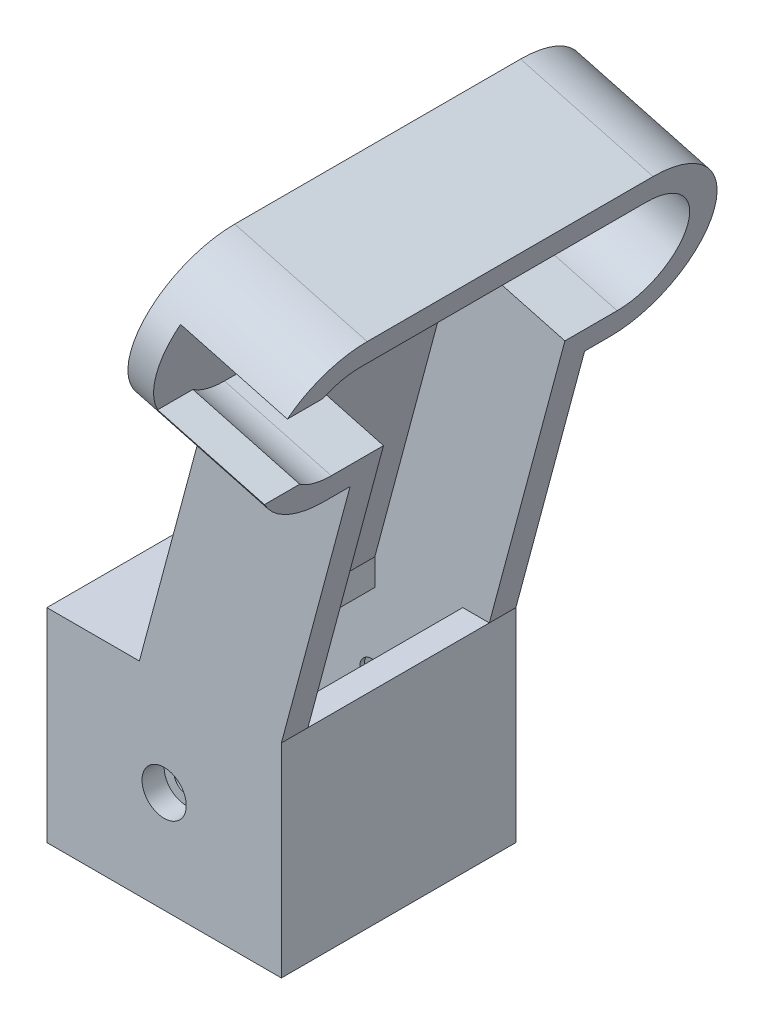
SolidWorks part; units mm, degrees
ref_plane "Front Plane" through (0, 0, 0) normal (0, 0, 1) x (1, 0, 0)
ref_plane "Top Plane" through (0, 0, 0) normal (0, 1, 0) x (1, 0, 0)
ref_plane "Right Plane" through (0, 0, 0) normal (1, 0, 0) x (0, 0, -1)
sketch "Sketch1" plane through (0, 0, 0) normal (0, 1, 0) x (1, 0, 0)
  line L0 (-20.5, 20.5) -> (-20.5, -20.5)
  line L1 (-20, 20) -> (20, 20) construction
  line L2 (-20, 20) -> (-20, -20) construction
  line L3 (-20, -20) -> (20, -20) construction
  line L4 (20, 20) -> (20, -20) construction
  line L5 (-20, 20) -> (20, -20) construction
  line L6 (-20, -20) -> (20, 20) construction
  line L7 (-20.5, -20.5) -> (20.5, -20.5)
  line L8 (20.5, 20.5) -> (20.5, -20.5)
  line L9 (-20.5, 20.5) -> (20.5, 20.5)
  line L10 (-26.5, 26.5) -> (-26.5, -26.5)
  line L11 (-26.5, -26.5) -> (26.5, -26.5)
  line L12 (26.5, 26.5) -> (26.5, -26.5)
  line L13 (-26.5, 26.5) -> (26.5, 26.5)
  point P1 (0, 0)
  dimension "D1" = 40
  dimension "D2" = 0.5
  dimension "D3" = 6
extrude "Boss-Extrude1" add sketch "Sketch1" along normal blind 40
sketch "Sketch2" plane through (0, 40, 0) normal (0, 1, 0) x (1, 0, 0)
  line L4 (26.5, 26.5) -> (-26.5, 26.5)
  line L5 (-26.5, 26.5) -> (-26.5, -26.5)
  line L6 (-26.5, -26.5) -> (26.5, -26.5)
  line L7 (26.5, -26.5) -> (26.5, 26.5)
  line L8 (26.5, 26.5) -> (-26.5, 26.5)
  line L9 (-26.5, 26.5) -> (-26.5, -26.5)
  line L10 (-26.5, -26.5) -> (26.5, -26.5)
  line L11 (26.5, -26.5) -> (26.5, 26.5)
  dimension "D1" = 0
extrude "Boss-Extrude2" add sketch "Sketch2" along normal blind 6
ref_plane "Plane1" through (13.2248, -3.5436, 0) normal (-0.9659, 0.2588, 0) x (0, 0, -1)
sketch "Sketch3" plane through (13.2248, -3.5436, 0) normal (-0.9659, 0.2588, 0) x (0, 0, -1)
  line L1 (26.5, -31.2913) -> (-26.5, -31.2913)
  line L2 (26.5, -31.2913) -> (26.5, -111.2913)
  line L3 (26.5, -111.2913) -> (-26.5, -111.2913)
  line L4 (-26.5, -31.2913) -> (-26.5, -111.2913)
  line L5 (20.5, -37.2913) -> (20.5, -105.2913)
  line L6 (20.5, -105.2913) -> (-20.5, -105.2913)
  line L7 (-20.5, -37.2913) -> (-20.5, -105.2913)
  line L8 (20.5, -37.2913) -> (-20.5, -37.2913)
  line L9 (-26.5, -51.2913) -> (-26.5, -6.8587) construction
  line L10 (26.5, -51.2913) -> (26.5, -6.8587) construction
  line L11 (-26.5, -51.2913) -> (26.5, -51.2913) construction
  point P5 (-26.2486, -51.2913)
  point P6 (0, 0)
  point P13 (0, 0)
  dimension "D1" = 80
  dimension "D3" = 20
  dimension "D2" = 6
extrude "Boss-Extrude3" add sketch "Sketch3" along normal blind 31
sketch "Sketch4" plane through (13.2248, -3.5436, 0) normal (0.9659, -0.2588, 0) x (0, 0, -1)
  line L0 (-32.3, 129.9913) -> (32.3, 129.9913) construction
  line L1 (-32.3, 142.6913) -> (32.3, 142.6913)
  line L2 (-32.3, 117.2913) -> (32.3, 117.2913)
  line L3 (-32.3, 148.6913) -> (32.3, 148.6913)
  line L4 (-32.3, 111.2913) -> (32.3, 111.2913)
  line L5 (0, 111.2913) -> (0, 51.2913) construction
  line L6 (-26.5, 111.2913) -> (26.5, 111.2913) construction
  line L7 (-20.5, 51.2913) -> (20.5, 51.2913) construction
  arc A0 (-32.3, 142.6913) -> (-32.3, 117.2913) centre (-32.3, 129.9913) ccw
  arc A1 (32.3, 117.2913) -> (32.3, 142.6913) centre (32.3, 129.9913) ccw
  arc A2 (32.3, 111.2913) -> (32.3, 148.6913) centre (32.3, 129.9913) ccw
  arc A3 (-32.3, 148.6913) -> (-32.3, 111.2913) centre (-32.3, 129.9913) ccw
  point P2 (0, 129.9913)
  point P19 (0, 0)
  point P20 (0, 111.2913)
  dimension "D1" = 25.4
  dimension "D2" = 64.6
  dimension "D3" = 6
extrude "Boss-Extrude4" add sketch "Sketch4" against normal up to surface (31 mm away) up to face at (2.8577, 77.5406, 0)
sketch "Sketch5" plane through (-16.7189, 4.4798, 0) normal (-0.9659, 0.2588, 0) x (0, 0, 1)
  line L0 (-20.5, 42.9849) -> (20.5, 42.9849)
  line L10 (20.5, 42.9849) -> (26.5, 42.9849)
  line L11 (26.5, 42.9849) -> (26.5, 111.2913)
  line L12 (26.5, 111.2913) -> (32.3, 111.2913)
  line L13 (32.3, 148.6913) -> (-32.3, 148.6913)
  line L14 (-32.3, 111.2913) -> (-26.5, 111.2913)
  line L15 (-26.5, 111.2913) -> (-26.5, 42.9849)
  line L16 (-26.5, 42.9849) -> (-20.5, 42.9849)
  line L17 (-20.5, 42.9849) -> (-20.5, 105.2913)
  line L18 (-20.5, 105.2913) -> (20.5, 105.2913)
  line L19 (20.5, 105.2913) -> (20.5, 42.9849)
  line L20 (20.5, 42.9849) -> (26.5, 42.9849)
  line L21 (26.5, 42.9849) -> (26.5, 111.2913)
  line L22 (26.5, 111.2913) -> (32.3, 111.2913)
  line L23 (32.3, 148.6913) -> (-32.3, 148.6913)
  line L24 (-32.3, 111.2913) -> (-26.5, 111.2913)
  line L25 (-26.5, 111.2913) -> (-26.5, 42.9849)
  line L26 (-26.5, 42.9849) -> (-20.5, 42.9849)
  line L27 (-20.5, 42.9849) -> (-20.5, 105.2913) construction
  line L28 (-20.5, 105.2913) -> (20.5, 105.2913) construction
  line L29 (20.5, 105.2913) -> (20.5, 42.9849) construction
  arc A2 (32.3, 111.2913) -> (32.3, 148.6913) centre (32.3, 129.9913) ccw
  arc A3 (-32.3, 148.6913) -> (-32.3, 111.2913) centre (-32.3, 129.9913) ccw
  arc A4 (32.3, 111.2913) -> (32.3, 148.6913) centre (32.3, 129.9913) ccw
  arc A5 (-32.3, 148.6913) -> (-32.3, 111.2913) centre (-32.3, 129.9913) ccw
  dimension "D1" = 0
extrude "Boss-Extrude5" add sketch "Sketch5" against normal blind 6
sketch "Sketch6" plane through (13.2248, -3.5436, 0) normal (0.9659, -0.2588, 0) x (0, 0, -1)
  line L0 (-32.3, 117.2913) -> (32.3, 117.2913) construction
  line L1 (-20.5, 105.2913) -> (20.5, 105.2913)
  line L2 (-20.5, 105.2913) -> (-20.5, 117.2913)
  line L3 (-20.5, 117.2913) -> (20.5, 117.2913)
  line L4 (20.5, 105.2913) -> (20.5, 117.2913)
  line L5 (20.5, 105.2913) -> (20.5, 44.5926) construction
extrude "Cut-Extrude1" cut sketch "Sketch6" against normal up to surface (25 mm away) up to face at (8.4731, 75.3152, 0)
sketch "Sketch7" plane through (-16.7189, 4.4798, 0) normal (0.9659, -0.2588, 0) x (0, 0, -1)
  line L0 (-22.5, 129.9913) -> (22.5, 129.9913) construction
  line L1 (-20.5, 117.2913) -> (-20.5, 142.6913) construction
  line L2 (32.3, 142.6913) -> (-32.3, 142.6913) construction
  point P0 (-22.5, 129.9913)
  point P1 (22.5, 129.9913)
  point P2 (0, 129.9913)
  point P9 (-20.5, 129.9913)
  dimension "D1" = 45
sketch "Sketch12" plane through (-16.7189, 4.4798, 0) normal (-0.9659, 0.2588, 0) x (0, 0, 1)
  point P0 (22.5, 129.9913)
  point P3 (-22.5, 129.9913)
hole_wizard "CBORE for M3 SHCS2" positions "Sketch12" profile "Sketch11" counterbore size "M3" standard "ANSI Metric" end condition up to next
sketch "Sketch11" plane through (16.9254, 130.0418, 22.5) normal (0, 0, 1) x (-0.2588, -0.9659, 0)
  line L0 (0, 0) -> (0, 6)
  line L1 (0, 6) -> (1.7, 6)
  line L3 (1.7, 6) -> (1.7, 3)
  line L4 (1.7, 3) -> (3.25, 3)
  line L5 (3.25, 3) -> (3.25, 0)
  line L7 (3.25, 0) -> (0, 0)
  line L11 (0, -6.35) -> (0, 107.95) construction
  dimension "Thru Hole Dia." = 3.4
  dimension "Thru Hole Depth" = 6
  dimension "C'Bore Dia." = 6.5
  dimension "C'Bore Depth" = 3
sketch "Sketch13" plane through (0, 0, 0) normal (0, 0, 1) x (1, 0, 0)
  line L0 (49.4572, 131.6776) -> (44.2809, 112.3591)
  line L1 (42.0291, 103.9555) -> (51.709, 140.0812) construction
  line L2 (44.2809, 112.3591) -> (20.1327, 118.8296)
  line L3 (20.1327, 118.8296) -> (25.3091, 138.1481)
  line L4 (25.3091, 138.1481) -> (49.4572, 131.6776)
  line L5 (12.0854, 111.9789) -> (42.0291, 103.9555) construction
  line L6 (21.7653, 148.1046) -> (12.0854, 111.9789) construction
  line L7 (16.9254, 130.0418) -> (46.8691, 122.0184) construction
  dimension "D1" = 6
  dimension "D2" = 20
extrude "Cut-Extrude2" cut sketch "Sketch13" along normal up to next
sketch "Sketch14" plane through (0, 0, 0) normal (0, -1, 0) x (1, 0, 0)
  line L0 (20.5, 20.5) -> (20.5, -20.5) construction
  line L1 (20.5, 20.5) -> (20.5, -20.5)
  line L2 (20.5, -20.5) -> (-20.5, -20.5) construction
  line L3 (-20.5, -20.5) -> (-20.5, 20.5) construction
  line L4 (-20.5, 20.5) -> (20.5, 20.5) construction
  line L5 (20.5, -20.5) -> (-20.5, -20.5)
  line L6 (-20.5, -20.5) -> (-20.5, 20.5)
  line L7 (-20.5, 20.5) -> (20.5, 20.5)
extrude "Cut-Extrude3" cut sketch "Sketch14" against normal up to surface (40 mm away) up to face at (-13.8506, 40, 0)
sketch "Sketch15" plane through (0, 46, 0) normal (0, 1, 0) x (1, 0, 0)
  line L0 (20.5, -20.5) -> (20.5, 20.5) construction
  line L1 (20.5, -20.5) -> (20.5, 20.5)
  line L4 (26.5, 20.5) -> (0.6181, 20.5)
  line L5 (0.6181, 20.5) -> (0.6181, -20.5)
  line L6 (0.6181, -20.5) -> (26.5, -20.5)
  line L7 (26.5, -20.5) -> (26.5, 20.5)
  line L8 (26.5, 20.5) -> (0.6181, 20.5)
  line L9 (0.6181, 20.5) -> (0.6181, -20.5)
  line L10 (0.6181, -20.5) -> (26.5, -20.5)
  line L11 (26.5, -20.5) -> (26.5, 20.5)
  line M5 (26.5, 20.5) -> (0.6181, 20.5)
  line M6 (0.6181, 20.5) -> (0.6181, -20.5)
  line M7 (0.6181, -20.5) -> (26.5, -20.5)
  dimension "D1" = 0
extrude "Cut-Extrude4" cut sketch "Sketch15" against normal up to next contours L1 M7 M5 M6 region at (10.559, 46, 0)
hole_wizard "CBORE for M5 SHCS1" positions "3DSketch4" profile "Sketch19" counterbore size "M5" standard "ANSI Metric" end condition up to next
sketch3d "3DSketch4"
  line L0 (26.5, 23, 26.5) -> (-26.5, 23, 26.5) construction
  line L1 (26.5, 46, 26.5) -> (26.5, 0, 26.5) construction
  line L2 (-26.5, 46, 26.5) -> (-26.5, 0, 26.5) construction
  line L3 (-26.5, 23, 26.5) -> (-26.5, 23, -26.5) construction
  line L4 (-26.5, 46, -26.5) -> (-26.5, 0, -26.5) construction
  line L5 (-26.5, 23, -26.5) -> (26.5, 23, -26.5) construction
  line L6 (26.5, 46, -26.5) -> (26.5, 0, -26.5) construction
  point P0 (0, 23, -26.5)
  point P2 (-26.5, 23, 0)
  point P4 (0, 23, 26.5)
  point P20 (0, 23, 26.5)
  point P21 (0, 0, 0)
  point P22 (-26.5, 23, 0)
  point P23 (0, 0, 0)
  point P24 (0, 23, -26.5)
  point P25 (0, 0, 0)
sketch "Sketch19" plane through (0, 23, -26.5) normal (1, 0, 0) x (0, 1, 0)
  line L0 (0, 0) -> (0, 6)
  line L1 (0, 6) -> (2.75, 6)
  line L3 (2.75, 6) -> (2.75, 5)
  line L4 (2.75, 5) -> (5, 5)
  line L5 (5, 5) -> (5, 0)
  line L7 (5, 0) -> (0, 0)
  line L11 (0, -6.35) -> (0, 107.95) construction
  dimension "Thru Hole Dia." = 5.5
  dimension "Thru Hole Depth" = 6
  dimension "C'Bore Dia." = 10
  dimension "C'Bore Depth" = 5
equation "\"D2@Sketch4\"=90-25.4"
